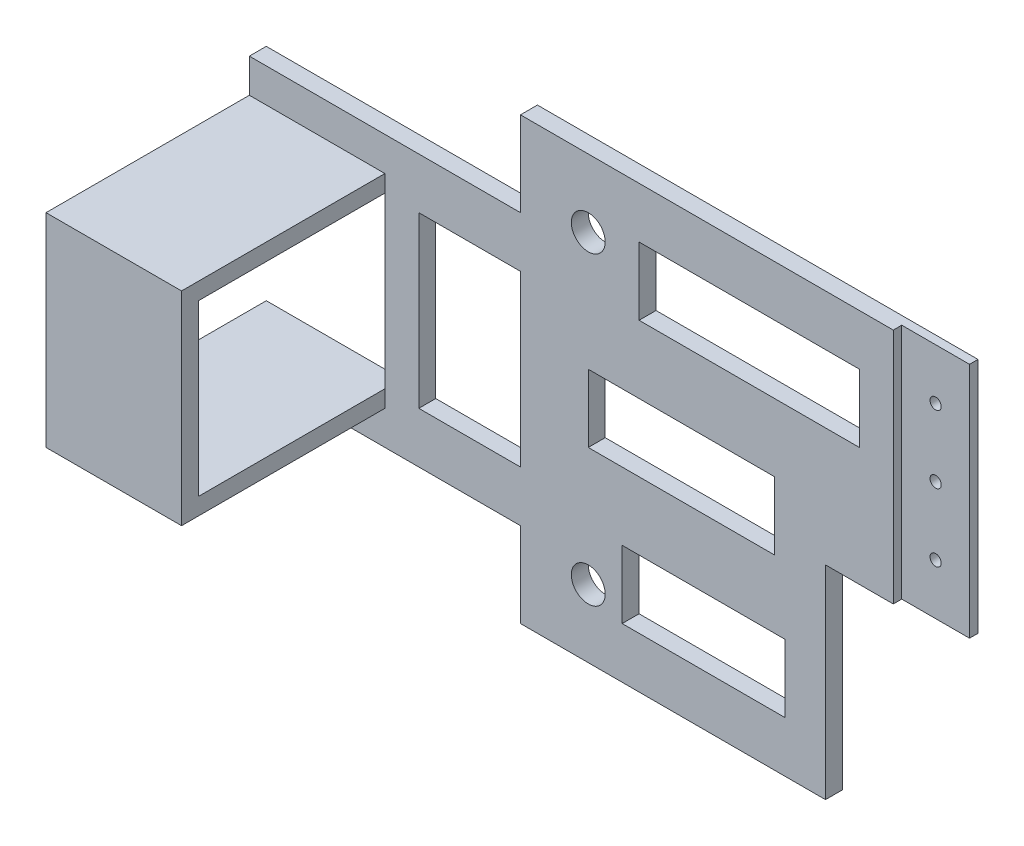
SolidWorks part; units mm, degrees
ref_plane "Front Plane" through (0, 0, 0) normal (0, 0, 1) x (1, 0, 0)
ref_plane "Top Plane" through (0, 0, 0) normal (0, 1, 0) x (1, 0, 0)
ref_plane "Right Plane" through (0, 0, 0) normal (1, 0, 0) x (0, 0, -1)
sketch "Sketch2" plane through (0, 0, 0) normal (0, 0, 1) x (1, 0, 0)
  line L0 (-69.85, -82.55) -> (-69.85, -6.35)
  line L1 (-184.15, -82.55) -> (-69.85, -82.55)
  line L2 (-184.15, -82.55) -> (-184.15, 82.55)
  line L5 (-184.15, 82.55) -> (-19.05, 82.55)
  line L6 (-19.05, -1025.0662) -> (-19.05, 48974.9338) construction
  line L14 (-19.05, -6.35) -> (-19.05, 82.55)
  line L17 (-69.85, -6.35) -> (-19.05, -6.35)
  point P0 (0, 0)
  dimension "D5" = 50.8
  dimension "D3" = 114.3
extrude "Boss-Extrude1" add sketch "Sketch2" along normal blind 6.35 contours L0 L17 L14 L5 L2 L1
sketch "Sketch5" plane through (0, 0, 6.35) normal (0, 0, 1) x (1, 0, 0)
  line L1 (-184.15, -82.55) -> (-69.85, -82.55) construction
  line L3 (-184.15, -82.55) -> (-184.15, 82.55) construction
  line L4 (-184.15, 82.55) -> (184.15, 82.55) construction
  circle A0 centre (-158.75, 57.15) radius 6.35
  circle A1 centre (-158.75, -57.15) radius 6.35
  dimension "D4" = 25.4
  dimension "D6" = 25.4
  dimension "D7" = 25.4
extrude "Cut-Extrude1" cut sketch "Sketch5" against normal through all contours A0 | A1
sketch "Sketch6" plane through (0, 0, 6.35) normal (0, 0, 1) x (1, 0, 0)
  line L8 (-139.7, 63.5) -> (-57.15, 63.5)
  line L9 (-139.7, 63.5) -> (-139.7, 38.1)
  line L10 (-57.15, 63.5) -> (-57.15, 38.1)
  line L11 (-139.7, 38.1) -> (-57.15, 38.1)
  line L12 (-184.15, -82.55) -> (-184.15, 82.55) construction
  line L23 (-146.05, -38.1) -> (-85.09, -38.1)
  line L24 (-146.05, -38.1) -> (-146.05, -63.5)
  line L25 (-85.09, -38.1) -> (-85.09, -63.5)
  line L26 (-146.05, -63.5) -> (-85.09, -63.5)
  line L27 (-158.75, 12.7) -> (-88.9, 12.7)
  line L36 (-184.15, 82.55) -> (-19.05, 82.55) construction
  line L37 (-69.85, -82.55) -> (-69.85, -6.35) construction
  line L38 (-184.15, -82.55) -> (-69.85, -82.55) construction
  line L39 (-19.05, -6.35) -> (-19.05, 82.55) construction
  line L40 (-158.75, 12.7) -> (-158.75, -12.7)
  line L41 (-158.75, -12.7) -> (-88.9, -12.7)
  line L42 (-88.9, 12.7) -> (-88.9, -12.7)
  point P15 (-69.85, -44.45)
  dimension "D2" = 38.1
  dimension "D3" = 15.24
  dimension "D4" = 19.05
  dimension "D5" = 38.1
  dimension "D6" = 44.45
  dimension "D7" = 25.4
  dimension "D8" = 25.4
  dimension "D9" = 25.4
  dimension "D10" = 25.4
  dimension "D11" = 19.05
  dimension "D12" = 25.4
  dimension "D18" = 19.05
extrude "Cut-Extrude2" cut sketch "Sketch6" against normal blind 10.16 contours L24 L26 L25 L23 | L9 L11 L10 L8 region at (-98.425, 50.8, 6.35) region at (-115.57, -50.8, 6.35)
hole_wizard "M5x0.8 Tapped Hole1" positions "Sketch10" profile "Sketch11" tap size "M5x0.8" standard "ANSI Metric"
sketch "Sketch10" plane through (0, 0, 6.35) normal (0, 0, 1) x (1, 0, 0)
  line L0 (-184.15, 82.55) -> (-19.05, 82.55) construction
  line L1 (-69.85, -6.35) -> (-19.05, -6.35) construction
  line L2 (-19.05, -6.35) -> (-19.05, 82.55) construction
  point P0 (-31.75, 63.5)
  point P2 (-31.75, 38.1)
  point P4 (-31.75, 12.7)
  point P7 (-31.75, 12.7)
  dimension "D1" = 25.4
  dimension "D2" = 25.4
  dimension "D3" = 19.05
  dimension "D4" = 19.05
  dimension "D5" = 12.7
  dimension "D6" = 12.7
sketch "Sketch11" plane through (-31.75, 63.5, 6.35) normal (1, 0, 0) x (0, -1, 0)
  line L0 (0, 0) -> (0, 15.2318)
  line L1 (0, 15.2318) -> (2.1, 13.97)
  line L2 (2.1, 13.97) -> (2.1, 0)
  line L5 (2.1, 0) -> (0, 0)
  line L10 (0, 15.2318) -> (-2.1, 13.97) construction
  line L11 (0, -6.35) -> (0, 107.95) construction
  dimension "Tap Drill Dia." = 4.2
  dimension "Tap Drill Depth" = 13.97
  dimension "Drill Angle" = 118
cosmetic thread "Hole Thread1" parameters "D1"=7.62, "D2"=5
cosmetic thread "Hole Thread2" parameters "D1"=7.62, "D2"=5
cosmetic thread "Hole Thread3" parameters "D1"=7.62, "D2"=5
cosmetic thread "Hole Thread4" parameters "D1"=7.62, "D2"=5
sketch "Sketch13" plane through (0, 0, 6.35) normal (0, 0, 1) x (1, 0, 0)
  line L0 (-184.15, -82.55) -> (-184.15, 82.55) construction
  line L1 (-184.15, 50.8) -> (-285.75, 50.8)
  line L2 (-184.15, 50.8) -> (-184.15, -50.8)
  line L3 (-184.15, -50.8) -> (-285.75, -50.8)
  line L4 (-285.75, 50.8) -> (-285.75, -50.8)
  line L5 (-184.15, 82.55) -> (-19.05, 82.55) construction
  dimension "D1" = 101.6
  dimension "D2" = 101.6
  dimension "D3" = 31.75
extrude "Boss-Extrude2" add sketch "Sketch13" against normal blind 6.35
sketch "Sketch14" plane through (0, 0, 6.35) normal (0, 0, 1) x (1, 0, 0)
  line L0 (-285.75, 50.8) -> (-285.75, -50.8) construction
  line L1 (-285.75, 38.1) -> (-234.95, 38.1)
  line L2 (-285.75, 38.1) -> (-285.75, -38.1)
  line L3 (-285.75, -38.1) -> (-234.95, -38.1)
  line L4 (-234.95, 38.1) -> (-234.95, -38.1)
  line L5 (-184.15, 50.8) -> (-285.75, 50.8) construction
  dimension "D1" = 12.7
  dimension "D2" = 76.2
  dimension "D3" = 50.8
extrude "Boss-Extrude3" add sketch "Sketch14" along normal blind 76.2
sketch "Sketch15" plane through (-285.75, 0, 0) normal (-1, 0, 0) x (0, 0, 1)
  line L0 (82.55, 38.1) -> (82.55, -38.1) construction
  line L1 (76.2, 31.75) -> (12.7, 31.75)
  line L2 (76.2, 31.75) -> (76.2, -31.75)
  line L3 (76.2, -31.75) -> (12.7, -31.75)
  line L4 (12.7, 31.75) -> (12.7, -31.75)
  line L5 (82.55, 38.1) -> (6.35, 38.1) construction
  line L6 (82.55, -38.1) -> (6.35, -38.1) construction
  line L7 (6.35, -38.1) -> (6.35, -50.8) construction
  dimension "D1" = 6.35
  dimension "D2" = 6.35
  dimension "D3" = 6.35
  dimension "D4" = 6.35
extrude "Cut-Extrude4" cut sketch "Sketch15" against normal through all
sketch "Sketch16" plane through (0, 0, 6.35) normal (0, 0, 1) x (1, 0, 0)
  line L0 (-19.05, -6.35) -> (-19.05, 82.55) construction
  line L1 (-19.05, 82.55) -> (-44.45, 82.55)
  line L2 (-19.05, 82.55) -> (-19.05, -6.35)
  line L3 (-19.05, -6.35) -> (-44.45, -6.35)
  line L4 (-44.45, 82.55) -> (-44.45, -6.35)
  line L5 (-184.15, 82.55) -> (-19.05, 82.55) construction
  line L6 (-69.85, -6.35) -> (-19.05, -6.35) construction
  dimension "D1" = 25.4
extrude "Cut-Extrude5" cut sketch "Sketch16" against normal blind 3.175
extrude "Cut-Extrude6" cut sketch "Sketch6<3>" against normal through all
sketch "Sketch6<3>" plane through (0, 0, 6.35) normal (0, 0, 1) x (1, 0, 0) same geometry as "Sketch6"
sketch "Sketch17" plane through (0, 0, 6.35) normal (0, 0, 1) x (1, 0, 0)
  line L40 (-222.25, 31.75) -> (-184.15, 31.75)
  line L41 (-222.25, 31.75) -> (-222.25, -31.75)
  line L42 (-222.25, -31.75) -> (-184.15, -31.75)
  line L43 (-184.15, 31.75) -> (-184.15, -31.75)
  line L44 (-184.15, 50.8) -> (-285.75, 50.8) construction
  dimension "D1" = 19.05
  dimension "D6" = 63.5
extrude "Cut-Extrude7" cut sketch "Sketch17" against normal through all
sketch "Sketch19" plane through (0, 0, 12.7) normal (0, 0, 1) x (1, 0, 0)
  line L0 (-285.75, 38.1) -> (-285.75, -38.1) construction
  line L1 (-285.75, 30.48) -> (-234.95, 30.48)
  line L2 (-285.75, 30.48) -> (-285.75, -30.48)
  line L3 (-285.75, -30.48) -> (-234.95, -30.48)
  line L4 (-234.95, 30.48) -> (-234.95, -30.48)
  line L5 (-234.95, -38.1) -> (-234.95, 38.1) construction
  line L6 (-234.95, 38.1) -> (-285.75, 38.1) construction
  line L7 (-285.75, -38.1) -> (-234.95, -38.1) construction
  dimension "D1" = 7.62
  dimension "D2" = 7.62
extrude "Cut-Extrude8" cut sketch "Sketch19" against normal through all
sketch "Sketch20" plane through (0, 0, 12.7) normal (0, 0, 1) x (1, 0, 0)
  line L1 (-285.75, 30.48) -> (-234.95, 30.48)
  line L2 (-285.75, 30.48) -> (-285.75, 31.75)
  line L3 (-285.75, 31.75) -> (-234.95, 31.75)
  line L4 (-234.95, 30.48) -> (-234.95, 31.75)
extrude "Cut-Extrude9" cut sketch "Sketch20" against normal through all
sketch "Sketch21" plane through (0, 0, 12.7) normal (0, 0, 1) x (1, 0, 0)
  line L1 (-285.75, -31.75) -> (-234.95, -31.75)
  line L2 (-285.75, -31.75) -> (-285.75, -30.48)
  line L3 (-285.75, -30.48) -> (-234.95, -30.48)
  line L4 (-234.95, -31.75) -> (-234.95, -30.48)
extrude "Cut-Extrude10" cut sketch "Sketch21" against normal through all contours L3 L4 L1 L2
